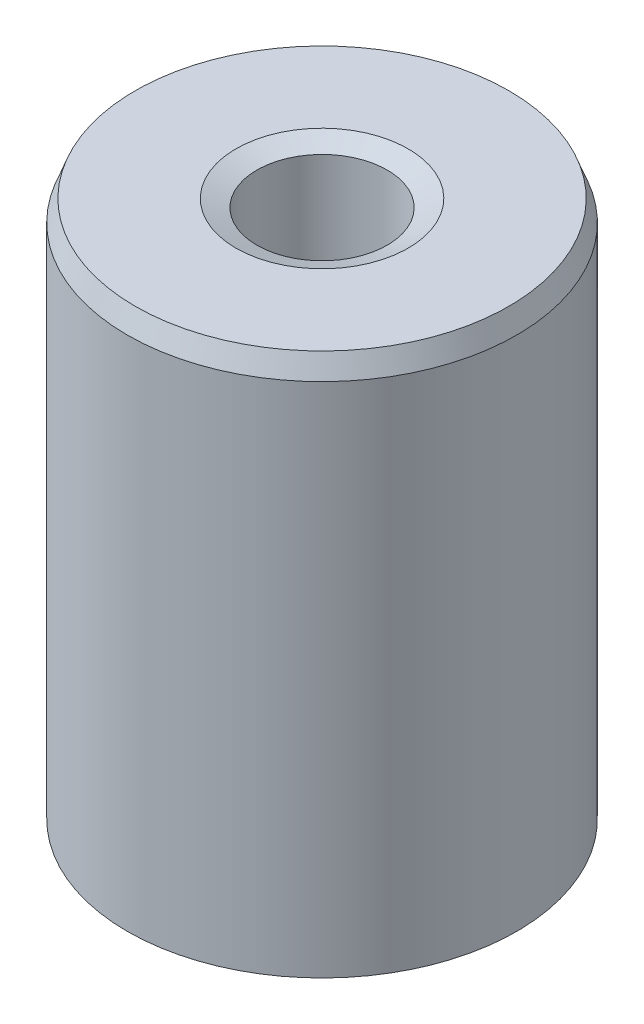
SolidWorks part; units mm, degrees
ref_plane "Front Plane" through (0, 0, 0) normal (0, 0, 1) x (1, 0, 0)
ref_plane "Top Plane" through (0, 0, 0) normal (0, 1, 0) x (1, 0, 0)
ref_plane "Right Plane" through (0, 0, 0) normal (1, 0, 0) x (0, 0, -1)
sketch "Sketch1" plane through (0, 0, 0) normal (0, 1, 0) x (1, 0, 0)
  circle A0 centre (0, 0) radius 10
  dimension "SLEEVE_OD" = 20
extrude "Boss-Extrude1" add sketch "Sketch1" along normal blind 28.0081
sketch "Sketch2" plane through (0, 0, 0) normal (0, 1, 0) x (1, 0, 0)
  circle A0 centre (0, 0) radius 3.3463
  dimension "BORE_D" = 6.6927
extrude "Cut-Extrude1" cut sketch "Sketch2" along normal through all
chamfer "Chamfer1" distance 1.0764 angle 20.652 4 edges at (0, 28.0081, 3.3463) (0, 0, 3.3463) (0, 0, 10) (0, 28.0081, 10) first distance on face at (0, 28.0081, 3.3463) first distance on face at (0, 0, 3.3463) first distance on face at (0, 28.0081, 10)
